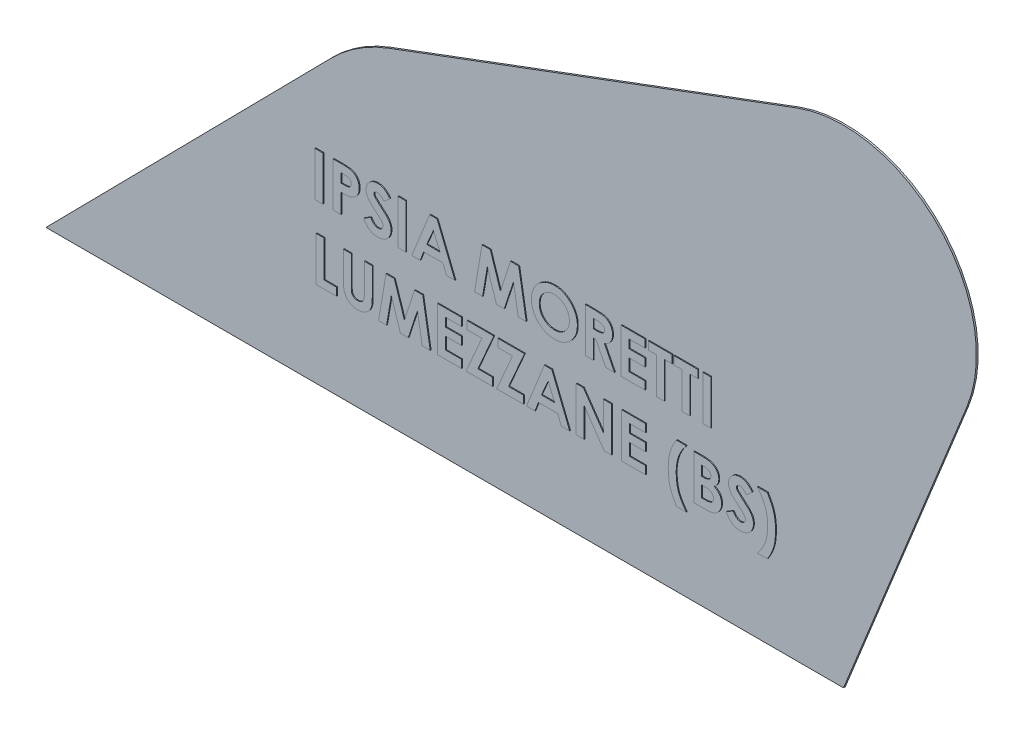
SolidWorks part; units mm, degrees
ref_plane "Piano frontale" through (0, 0, 0) normal (0, 0, 1) x (1, 0, 0)
ref_plane "Piano superiore" through (0, 0, 0) normal (0, 1, 0) x (1, 0, 0)
ref_plane "Piano destro" through (0, 0, 0) normal (1, 0, 0) x (0, 0, -1)
sketch "Schizzo1" plane through (0, 0, 0) normal (0, 0, 1) x (1, 0, 0)
  line L0 (0, 0) -> (900, 0)
  line L1 (0, 0) -> (321.8301, 326.3823)
  line L2 (387.0515, 368.6342) -> (847.5429, 540.5285)
  line L3 (1039.0537, 343.75) -> (900, 0)
  arc A0 (1039.0537, 343.75) -> (847.5429, 540.5285) centre (900, 400) ccw
  arc A1 (387.0515, 368.6342) -> (321.8301, 326.3823) centre (450, 200) ccw
  dimension "D1" = 150
  dimension "D2" = 180
  dimension "D6" = 450
  dimension "D3" = 900
  dimension "D4" = 400
  dimension "D5" = 200
extrude "Estrusione1" add sketch "Schizzo1" along normal mid plane 2
sketch "Schizzo8" plane through (0, 0, 1) normal (0, 0, 1) x (1, 0, 0)
  line L0 (0, 0) -> (900, 0) construction
  text T0 "IPSIA MORETTI\r\nLUMEZZANE (BS)" font "Century Gothic" height 50
  dimension "D1" = 300
  dimension "D2" = 180
extrude "Estrusione2" add sketch "Schizzo8" along normal blind 1
sketch "Schizzo9" plane through (0, 0, -1) normal (0, 0, -1) x (-1, 0, 0)
  line L0 (0, 0) -> (-900, 0) construction
  text T0 "IPSIA MORETTI\r\nLUMEZZANE (BS)" font "Century Gothic" height 50
  dimension "D1" = 180
  dimension "D2" = 100
extrude "Estrusione3" add sketch "Schizzo9" along normal blind 1
